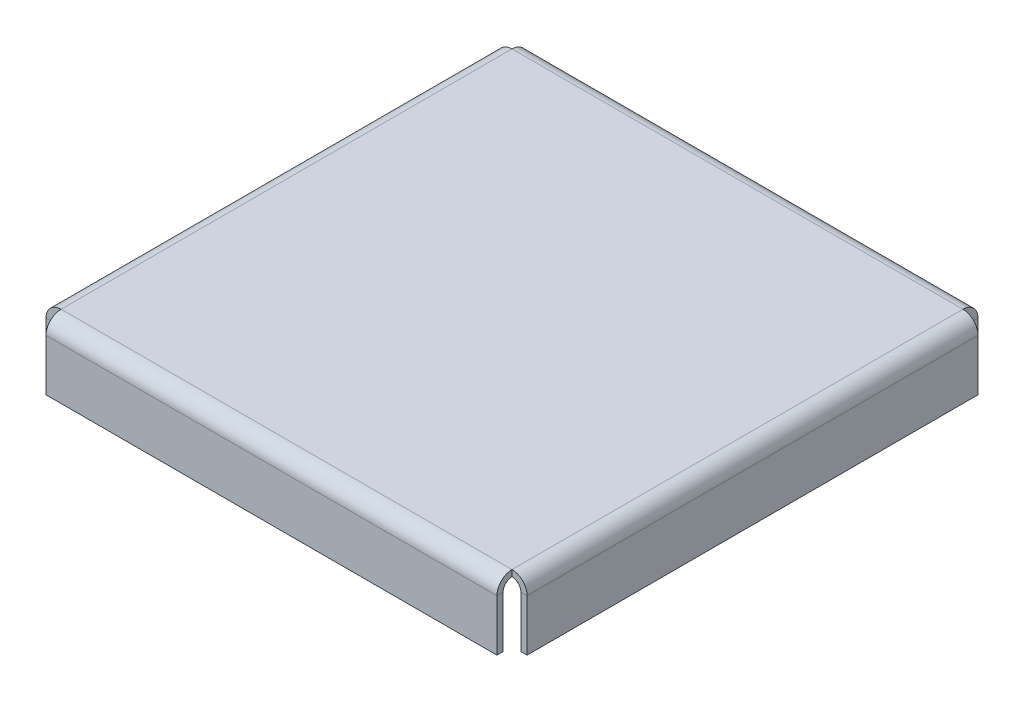
SolidWorks part; units mm, degrees
note: The reader was unsure of these and kept them because the rebuilt part matched: flange length of "Edge-Flange1", "Edge-Flange2", "Edge-Flange3", "Edge-Flange4".
ref_plane "Front Plane" through (0, 0, 0) normal (0, 0, 1) x (1, 0, 0)
ref_plane "Top Plane" through (0, 0, 0) normal (0, 1, 0) x (1, 0, 0)
ref_plane "Right Plane" through (0, 0, 0) normal (1, 0, 0) x (0, 0, -1)
sketch "Sketch1" plane through (0, 0, 0) normal (0, 1, 0) x (1, 0, 0)
  line L1 (-25.4, -25.4) -> (25.4, -25.4)
  line L2 (-25.4, -25.4) -> (-25.4, 25.4)
  line L3 (-25.4, 25.4) -> (25.4, 25.4)
  line L4 (25.4, -25.4) -> (25.4, 25.4)
  line L5 (-25.4, -25.4) -> (25.4, 25.4) construction
  line L6 (-25.4, 25.4) -> (25.4, -25.4) construction
  point P0 (0, 0)
  dimension "D1" = 50.8
  dimension "D2" = 50.8
base flange "Base-Flange1" sketch "Sketch1" thickness 0.7 reverse thickness direction no parameters "D1"=1
edge flange "Edge-Flange1" sketch "Sketch9" flange angle 90 flange length 7.5 flange position bend outside bend radius 1 thickness 0.7 relief rectangular parameters "D6"=0
sketch "Sketch9" plane through (25.4, -0.7, 0) normal (1, 0, 0) x (0, 0, 1)
  line L0 (25.4, 0) -> (-25.4, 0) construction
  line L1 (25.4, 0) -> (-25.4, 0)
  line L2 (-25.4, 0) -> (-25.4, 6.8)
  line L3 (-25.4, 6.8) -> (25.4, 6.8)
  line L4 (25.4, 6.8) -> (25.4, 0)
  dimension "D1" = 6.8
bend "EdgeBend1" bend radius 1 bend angle 90 parameters "D5"=1
edge flange "Edge-Flange2" sketch "Sketch12" flange angle 90 flange length 7.5 flange position bend outside bend radius 1 thickness 0.7 relief rectangular parameters "D6"=0
sketch "Sketch12" plane through (0, -0.7, 25.4) normal (0, 0, 1) x (-1, 0, 0)
  line L0 (25.4, 0) -> (-25.4, 0) construction
  line L1 (25.4, 0) -> (-25.4, 0)
  line L2 (-25.4, 0) -> (-25.4, 6.8)
  line L3 (-25.4, 6.8) -> (25.4, 6.8)
  line L4 (25.4, 6.8) -> (25.4, 0)
bend "EdgeBend2" bend radius 1 bend angle 90 parameters "D5"=2
edge flange "Edge-Flange3" sketch "Sketch15" flange angle 90 flange length 7.5 flange position bend outside bend radius 1 thickness 0.7 relief rectangular parameters "D6"=0
sketch "Sketch15" plane through (-25.4, -0.7, 0) normal (-1, 0, 0) x (0, 0, -1)
  line L0 (25.4, 0) -> (-25.4, 0) construction
  line L1 (25.4, 0) -> (-25.4, 0)
  line L2 (-25.4, 0) -> (-25.4, 6.8)
  line L3 (-25.4, 6.8) -> (25.4, 6.8)
  line L4 (25.4, 6.8) -> (25.4, 0)
bend "EdgeBend3" bend radius 1 bend angle 90 parameters "D5"=3
edge flange "Edge-Flange4" sketch "Sketch18" flange angle 90 flange length 7.5 flange position bend outside bend radius 1 thickness 0.7 relief rectangular parameters "D6"=0
sketch "Sketch18" plane through (0, -0.7, -25.4) normal (0, 0, 1) x (-1, 0, 0)
  line L1 (25.4, 0) -> (-25.4, 0) construction
  line L2 (-25.4, 0) -> (-25.4, 6.8)
  line L3 (-25.4, 6.8) -> (25.4, 6.8)
  line L4 (25.4, 6.8) -> (25.4, 0)
  line L5 (25.4, 0) -> (-25.4, 0)
bend "EdgeBend4" bend radius 1 bend angle 90 parameters "D5"=4
sketch "Bend-Lines1" [suppressed] plane through (0, 0, 0) normal (0, 1, 0) x (1, 0, 0)
sketch "Bounding-Box1" [suppressed] plane through (0, 0, 0) normal (0, 1, 0) x (1, 0, 0)
sheet metal parameters "Sheet-Metal1" thickness 0.7 parameters "D1"=1
flat pattern "Flat-Pattern1" [suppressed]
sketch "Bend-Lines2" plane through (0, 0, 0) normal (0, 1, 0) x (1, 0, 0)
sketch "Bounding-Box2" [suppressed] plane through (0, 0, 0) normal (0, 1, 0) x (1, 0, 0)
sheet metal parameters "Sheet-Metal2" thickness 0.7 parameters "D1"=1
flat pattern "Flat-Pattern1" [suppressed]
sketch "Bend-Lines2" plane through (0, 0, 0) normal (0, 1, 0) x (1, 0, 0)
sketch "Bounding-Box2" [suppressed] plane through (0, 0, 0) normal (0, 1, 0) x (1, 0, 0)
bend of the flat pattern "Flatten-<EdgeBend1>1"
sheet metal parameters "Sheet-Metal3" thickness 0.7 parameters "D1"=1
flat pattern "Flat-Pattern1" [suppressed]
sketch "Bend-Lines2" plane through (0, 0, 0) normal (0, 1, 0) x (1, 0, 0)
sketch "Bounding-Box2" [suppressed] plane through (0, 0, 0) normal (0, 1, 0) x (1, 0, 0)
bend of the flat pattern "Flatten-<EdgeBend1>1"
bend of the flat pattern "Flatten-<EdgeBend2>1"
sheet metal parameters "Sheet-Metal4" thickness 0.7 parameters "D1"=1
flat pattern "Flat-Pattern1" [suppressed]
sketch "Bend-Lines2" plane through (0, 0, 0) normal (0, 1, 0) x (1, 0, 0)
sketch "Bounding-Box2" [suppressed] plane through (0, 0, 0) normal (0, 1, 0) x (1, 0, 0)
bend of the flat pattern "Flatten-<EdgeBend1>1"
bend of the flat pattern "Flatten-<EdgeBend3>1"
bend of the flat pattern "Flatten-<EdgeBend2>1"
sheet metal parameters "Sheet-Metal5" thickness 0.7 parameters "D1"=1
flat pattern "Flat-Pattern1" [suppressed]
sketch "Bend-Lines2" plane through (0, 0, 0) normal (0, 1, 0) x (1, 0, 0)
sketch "Bounding-Box2" [suppressed] plane through (0, 0, 0) normal (0, 1, 0) x (1, 0, 0)
bend of the flat pattern "Flatten-<EdgeBend1>1"
bend of the flat pattern "Flatten-<EdgeBend3>1"
bend of the flat pattern "Flatten-<EdgeBend4>1"
bend of the flat pattern "Flatten-<EdgeBend2>1"
